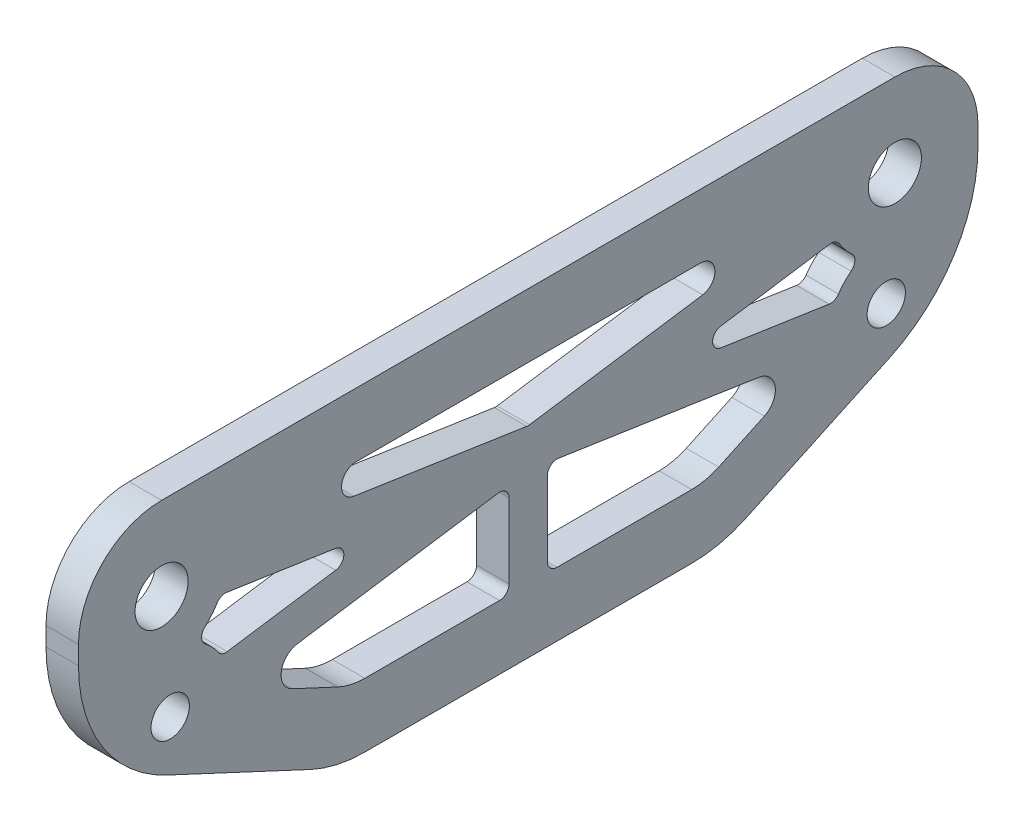
SolidWorks part; units mm, degrees
ref_plane "Front Plane" through (0, 0, 0) normal (0, 0, 1) x (1, 0, 0)
ref_plane "Top Plane" through (0, 0, 0) normal (0, 1, 0) x (1, 0, 0)
ref_plane "Right Plane" through (0, 0, 0) normal (1, 0, 0) x (0, 0, -1)
sketch "Sketch1" plane through (0, 0, 0) normal (1, 0, 0) x (0, 0, -1)
  line L0 (15, 12.5) -> (28.675, 12.5)
  line L1 (-15, -12.5) -> (15, -12.5)
  line L3 (-15, 12.5) -> (15, 12.5)
  line L5 (-15, -12.5) -> (15, 12.5) construction
  line L6 (-15, 12.5) -> (15, -12.5) construction
  line L8 (0, 12.5) -> (0, -12.5) construction
  line L10 (-15, 12.5) -> (-28.675, 12.5)
  line L11 (23.175, 177.6626) -> (23.175, -49.7374) construction
  line L13 (35.175, 6) -> (35.175, 4.5526)
  line L14 (28.2464, -6.3231) -> (15, -12.5)
  line L16 (-35.175, 6) -> (-35.175, 4.5526)
  line L17 (-28.2464, -6.3231) -> (-15, -12.5)
  arc A0 (28.675, 12.5) -> (35.175, 6) centre (28.675, 6) cw
  circle A1 centre (28.675, 6) radius 5.5 construction
  circle A2 centre (-28.675, 6) radius 5.5 construction
  arc A3 (-28.675, 12.5) -> (-35.175, 6) centre (-28.675, 6) ccw
  arc A4 (35.175, 4.5526) -> (28.2464, -6.3231) centre (23.175, 4.5526) cw
  circle A5 centre (28.675, 6) radius 2.075
  arc A6 (-35.175, 4.5526) -> (-28.2464, -6.3231) centre (-23.175, 4.5526) ccw
  circle A9 centre (-28.675, 6) radius 2.075
  circle A11 centre (28, -2.5) radius 1.5
  circle A12 centre (-28, -2.5) radius 1.5
  point P0 (0, 0)
  point P28 (0, 0)
  dimension "D1" = 11
  dimension "D2" = 1
  dimension "D3" = 4.15
  dimension "D4" = 3
  dimension "D6" = 25
  dimension "D8" = 12
  dimension "D5" = 25
  dimension "D7" = 30
  dimension "D9" = 28
  dimension "D10" = 2.5
extrude "Boss-Extrude1" add sketch "Sketch1" along normal blind 2.54
fillet "Fillet1" radius 10 2 edges at (1.27, -12.5, -15) (1.27, -12.5, 15)
sketch "Sketch2" plane through (0, 0, 0) normal (1, 0, 0) x (0, 0, -1)
  line L0 (-28.675, 6) -> (28, -2.5) construction
  line L10 (-28.675, -2.6012) -> (28.675, 6)
  line L11 (-28.675, 6) -> (28, -2.5)
  line L12 (-28.8975, 4.5166) -> (27.7775, -3.9834)
  line L13 (-28.4525, 7.4834) -> (28.2225, -1.0166)
  line L14 (-28.8975, 4.5166) -> (-28.4525, 7.4834)
  line L15 (27.7775, -3.9834) -> (28.2225, -1.0166)
  line L16 (-12.7831, -7.5) -> (12.7831, -7.5)
  line L17 (14.8961, -7.0315) -> (26.1333, -1.7916)
  line L18 (30.175, 4.5526) -> (30.175, 6)
  line L19 (28.675, 7.5) -> (-28.675, 7.5)
  line L20 (-30.175, 6) -> (-30.175, 4.5526)
  line L21 (-26.1333, -1.7916) -> (-14.8961, -7.0315)
  line L22 (-12.7831, -7.5) -> (12.7831, -7.5)
  line L23 (14.8961, -7.0315) -> (26.1333, -1.7916)
  line L24 (30.175, 4.5526) -> (30.175, 6)
  line L25 (28.675, 7.5) -> (-28.675, 7.5)
  line L26 (-30.175, 6) -> (-30.175, 4.5526)
  line L27 (-26.1333, -1.7916) -> (-14.8961, -7.0315)
  line L28 (-28.4525, -4.0846) -> (28.8975, 4.5166)
  line L29 (-28.8975, -1.1178) -> (28.4525, 7.4834)
  line L30 (-28.4525, -4.0846) -> (-28.8975, -1.1178)
  line L31 (28.8975, 4.5166) -> (28.4525, 7.4834)
  line L32 (0, -7.5) -> (0, 7.5) construction
  line L33 (0, 1.6994) -> (0, -7.5)
  line L34 (-1.5, 1.6994) -> (-1.5, -7.5)
  line L35 (1.5, 1.6994) -> (1.5, -7.5)
  line L36 (-1.5, 1.6994) -> (1.5, 1.6994)
  line L37 (-1.5, -7.5) -> (1.5, -7.5)
  arc A0 (-18.0527, -2.5249) -> (-18.4641, -5.3678) centre (-17.8302, -4.0083) ccw
  arc A1 (18.0527, -2.5249) -> (18.4641, -5.3678) centre (17.8302, -4.0083) cw
  circle A2 centre (-28, -2.5) radius 4.5
  circle A3 centre (-28, -2.5) radius 4.5
  circle A5 centre (28, -2.5) radius 4.5
  circle A6 centre (28, -2.5) radius 4.5
  circle A11 centre (-28.675, 6) radius 5.075
  arc A12 (12.7831, -7.5) -> (14.8961, -7.0315) centre (12.7831, -2.5) ccw
  arc A13 (26.1333, -1.7916) -> (30.175, 4.5526) centre (23.175, 4.5526) ccw
  arc A14 (30.175, 6) -> (28.675, 7.5) centre (28.675, 6) ccw
  arc A15 (-28.675, 7.5) -> (-30.175, 6) centre (-28.675, 6) ccw
  arc A16 (-30.175, 4.5526) -> (-26.1333, -1.7916) centre (-23.175, 4.5526) ccw
  arc A17 (-14.8961, -7.0315) -> (-12.7831, -7.5) centre (-12.7831, -2.5) ccw
  arc A18 (12.7831, -7.5) -> (14.8961, -7.0315) centre (12.7831, -2.5) ccw
  arc A19 (26.1333, -1.7916) -> (30.175, 4.5526) centre (23.175, 4.5526) ccw
  arc A20 (30.175, 6) -> (28.675, 7.5) centre (28.675, 6) ccw
  arc A21 (-28.675, 7.5) -> (-30.175, 6) centre (-28.675, 6) ccw
  arc A22 (-30.175, 4.5526) -> (-26.1333, -1.7916) centre (-23.175, 4.5526) ccw
  arc A23 (-14.8961, -7.0315) -> (-12.7831, -7.5) centre (-12.7831, -2.5) ccw
  circle A24 centre (-28.675, 6) radius 5.075
  circle A26 centre (28.675, 6) radius 5.075
  circle A27 centre (28.675, 6) radius 5.075
  arc A32 (13.477, 7.5) -> (13.6439, 5.2624) centre (13.477, 6.375) cw
  arc A33 (-13.477, 7.5) -> (-13.6439, 5.2624) centre (-13.477, 6.375) ccw
  dimension "D11" = 3
  dimension "D12" = 1.125
  dimension "D2" = 1.5
  dimension "D1" = 5
  dimension "D3" = 3
  dimension "D4" = 3
  dimension "D6" = 1.5
  dimension "D7" = 1.5
  dimension "D8" = 1.5
  dimension "D9" = 1.5
  dimension "D13" = 1.5
  dimension "D14" = 1.5
  dimension "D15" = 3
extrude "Cut-Extrude2" cut sketch "Sketch2" along normal through all contours A24 A3 L29 L12 | A27 L28 L13 A6 | L25 A33 L13 L29 A32 | A1 L12 L35 L22 | L28 A0 L22 L34 region at (0, 1.7005, 19.9688) region at (0, -4.2389, 9.1911) region at (0, 5.8357, 0) region at (0, -4.2389, -9.1911) region at (0, 1.7005, -19.9688)
fillet "Fillet2" radius 0.75 13 edges at (1.27, -7.5, -1.5) (1.27, 3.7975, -24.1028) (1.27, 1.6994, -10.1133) (1.27, 3.7975, 24.1028) (1.27, 3.2162, 0) (1.27, -0.0424, -1.5) (1.27, -7.5, 1.5) (1.27, -0.0424, 1.5) (1.27, 1.6994, 10.1133) (1.27, -0.3873, -24.0268) (1.27, 1.6002, -26.1457) (1.27, -0.3873, 24.0268) (1.27, 1.6002, 26.1457)
